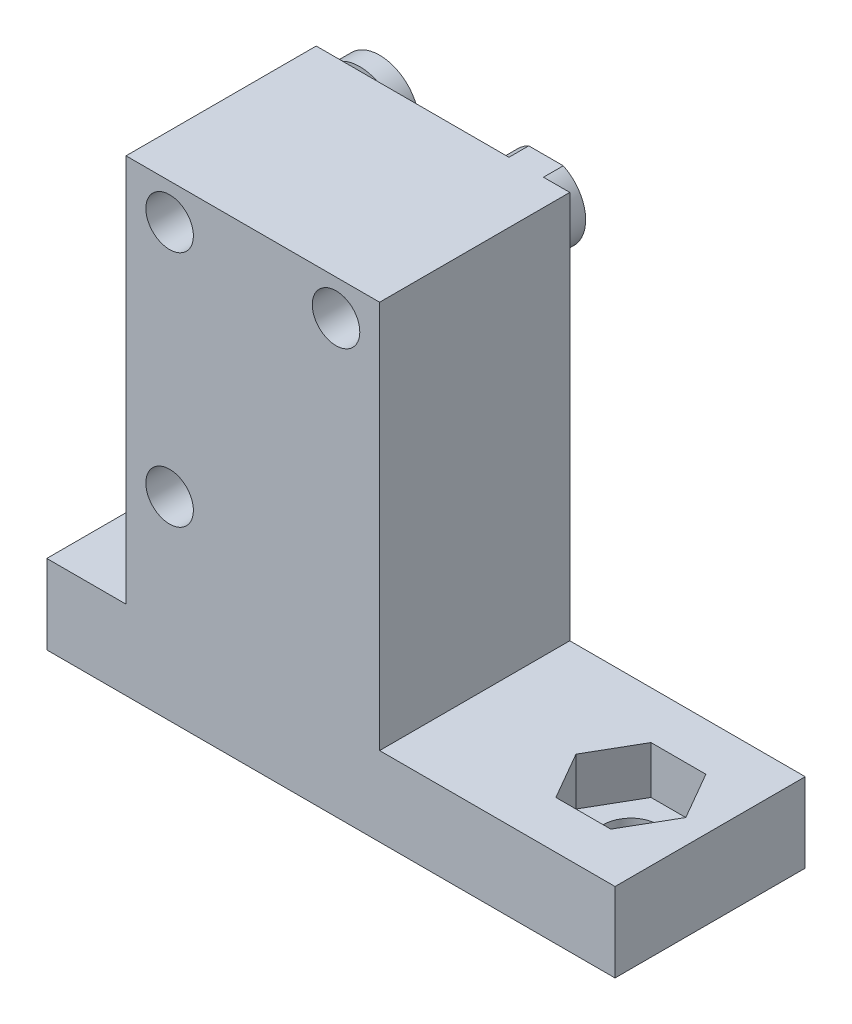
SolidWorks part; units mm, degrees
ref_plane "Front Plane" through (0, 0, 0) normal (0, 0, 1) x (1, 0, 0)
ref_plane "Top Plane" through (0, 0, 0) normal (0, 1, 0) x (1, 0, 0)
ref_plane "Right Plane" through (0, 0, 0) normal (1, 0, 0) x (0, 0, -1)
sketch "Sketch1" plane through (0, 0, 0) normal (0, 0, 1) x (1, 0, 0)
  line L1 (0, 19.75) -> (16, 19.75)
  line L2 (0, 19.75) -> (0, -9.65)
  line L3 (0, -9.65) -> (16, -9.65)
  line L4 (16, 19.75) -> (16, -9.65)
  circle A0 centre (2.75, 2.5) radius 2.5
  circle A1 centre (2.75, 2.5) radius 1.5
  circle A2 centre (2.75, 17.5) radius 1.5
  circle A3 centre (2.75, 17.5) radius 2.5
  circle A4 centre (13.25, 17.5) radius 1.5
  circle A5 centre (13.25, 17.5) radius 2.5
  dimension "D2" = 3
  dimension "D3" = 5
  dimension "D4" = 3
  dimension "D5" = 5
  dimension "D6" = 3
  dimension "D7" = 5
extrude "Boss-Extrude1" add sketch "Sketch1" along normal up to surface (1.25 mm away) contours A0 A1 | L1 A5 A4 | A2 | A3 region at (13.25, 19.681, 0) region at (0.3207, 2.5, 0) region at (2.75, 17.5, 0)
extrude "Boss-Extrude2" add sketch "Sketch1<3>" along normal up to surface (12 mm away) from surface contours A5 L1 A3 L2 L3 L4 A0 | A0 A1 | L1 A3 A2 | L1 A5 A4 region at (8.2501, 4.0118, 0) region at (2.75, 19.681, 0) region at (13.25, 19.681, 0) region at (0.3207, 2.5, 0) starting at face at (2.75, 1, 1.25)
sketch "Sketch1<3>" plane through (0, 0, 0) normal (0, 0, 1) x (1, 0, 0) same geometry as "Sketch1"
sketch "Sketch2" plane through (0, -9.75, 0) normal (0, 1, 0) x (1, 0, 0)
  line L1 (30.854, -13.25) -> (-5, -13.25)
  line L2 (30.854, -13.25) -> (30.854, -1.25)
  line L3 (30.854, -1.25) -> (-5, -1.25)
  line L4 (-5, -13.25) -> (-5, -1.25)
  line L6 (0, -13.25) -> (0, -1.25) construction
  line L7 (0, -13.25) -> (16, -13.25) construction
  line L8 (29.3181, -7.25) -> (27.5861, -4.25)
  line L9 (27.5861, -4.25) -> (24.122, -4.25)
  line L10 (24.122, -4.25) -> (22.3899, -7.25)
  line L11 (22.3899, -7.25) -> (24.122, -10.25)
  line L12 (24.122, -10.25) -> (27.5861, -10.25)
  line L13 (27.5861, -10.25) -> (29.3181, -7.25)
  line L14 (-361.146, -1.25) -> (87.854, -1.25) construction
  circle A0 centre (25.854, -7.25) radius 1.75 construction
  circle A1 centre (0.854, -7.25) radius 1.4
  circle A2 centre (25.854, -7.25) radius 1.5
  circle A3 centre (25.854, -7.25) radius 3 construction
  line M5 (-361.146, -12.75) -> (87.854, -12.75)
  line M7 (87.854, -1.75) -> (-361.146, -1.75)
  circle M17 centre (0.854, -7.25) radius 1.75
  circle M18 centre (25.854, -7.25) radius 1.75
  dimension "D1" = 5
  dimension "D3" = 3
  dimension "D4" = 2.8
  dimension "D5" = 6
  dimension "D2" = 5
  dimension "D6" = 0
  dimension "D7" = 0
extrude "Boss-Extrude3" add sketch "Sketch2" along normal blind 5 contours L2 L1 L4 L3 | L8 L9 L10 L11 L12 L13
extrude "Boss-Extrude4" add sketch "Sketch2<3>" along normal blind 3 contours L4 L2 L13 L12 L11 L10 L9 L8 M5 M7 M17 | A1 region at (12.1157, -9.75, 7.25) region at (0.854, -9.75, 7.25)
sketch "Sketch2<3>" plane through (0, -9.75, 0) normal (0, 1, 0) x (1, 0, 0) same geometry as "Sketch2"
extrude "Cut-Extrude1" cut sketch "Sketch2<4>" along normal blind 10 contours A1 region at (0.854, -9.75, 7.25)
sketch "Sketch2<4>" plane through (0, -9.75, 0) normal (0, 1, 0) x (1, 0, 0) same geometry as "Sketch2"
extrude "Boss-Extrude5" add sketch "Sketch2<5>" along normal blind 2 contours L12 L13 L8 L9 L10 L11 M18 region at (28.3727, -9.75, 8.7042)
sketch "Sketch2<5>" plane through (0, -9.75, 0) normal (0, 1, 0) x (1, 0, 0) same geometry as "Sketch2"
